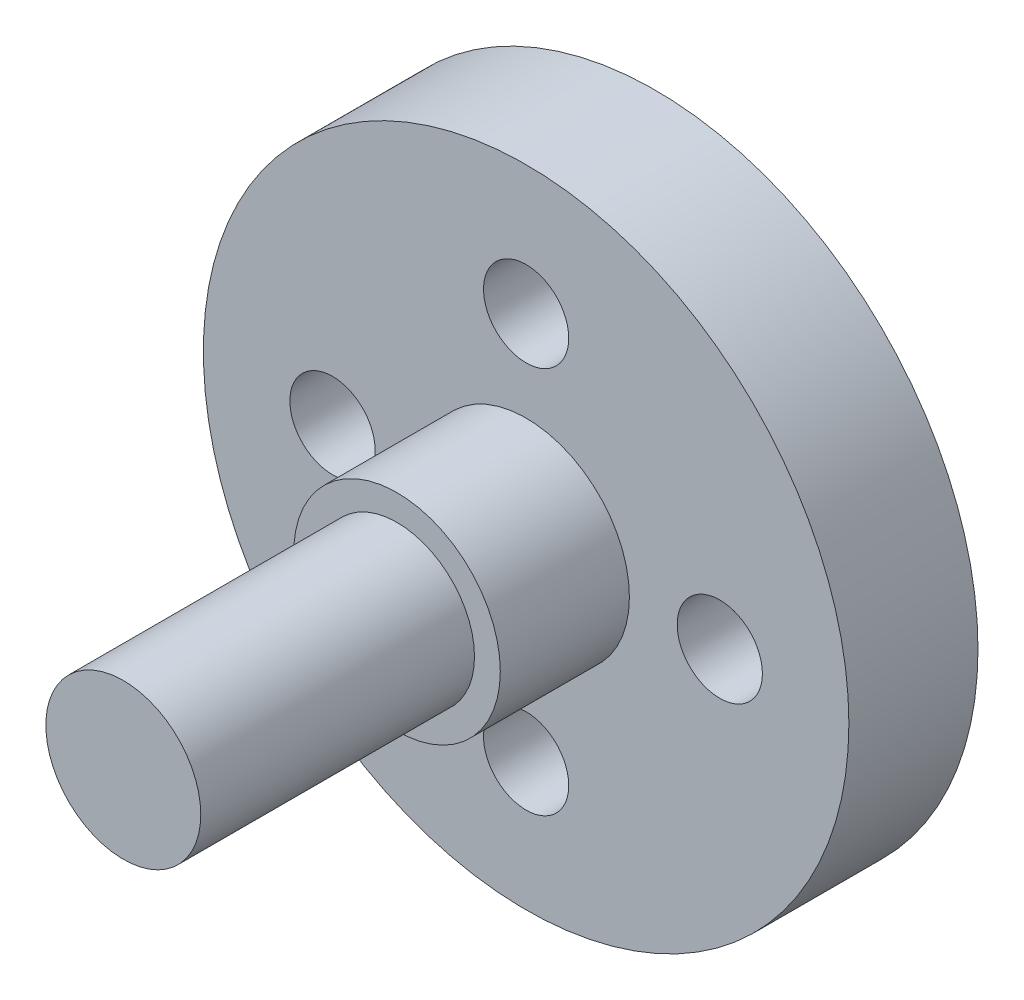
SolidWorks part; units mm, degrees
material "5052-H34"
ref_plane "正面" through (0, 0, 0) normal (0, 0, 1) x (1, 0, 0)
ref_plane "平面" through (0, 0, 0) normal (0, 1, 0) x (1, 0, 0)
ref_plane "右側面" through (0, 0, 0) normal (1, 0, 0) x (0, 0, -1)
sketch "ｽｹｯﾁ1" plane through (0, 0, 0) normal (0, 0, 1) x (1, 0, 0)
  circle A0 centre (0, 0) radius 12.5
  dimension "D1" = 25
extrude "ﾎﾞｽ - 押し出し1" add sketch "ｽｹｯﾁ1" along normal blind 5
sketch "ｽｹｯﾁ2" plane through (0, 0, 5) normal (0, 0, 1) x (1, 0, 0)
  circle A0 centre (0, 0) radius 4
  dimension "D1" = 8
extrude "ﾎﾞｽ - 押し出し2" add sketch "ｽｹｯﾁ2" along normal blind 5
sketch "ｽｹｯﾁ3" plane through (0, 0, 10) normal (0, 0, 1) x (1, 0, 0)
  circle A0 centre (0, 0) radius 3
  dimension "D1" = 6
extrude "ﾎﾞｽ - 押し出し3" add sketch "ｽｹｯﾁ3" along normal blind 10.6
sketch "ｽｹｯﾁ4" plane through (0, 0, 5) normal (0, 0, 1) x (1, 0, 0)
  line L0 (0, 0) -> (0, 7.5) construction
  circle A0 centre (0, 7.5) radius 1.65
  circle A1 centre (7.5, 0) radius 1.65
  circle A2 centre (0, -7.5) radius 1.65
  circle A3 centre (-7.5, 0) radius 1.65
  point P13 (0, 0)
  dimension "D1" = 3.3
  dimension "D3" = 15
  dimension "D2" = 4
extrude "ｶｯﾄ - 押し出し1" cut sketch "ｽｹｯﾁ4" against normal through all
